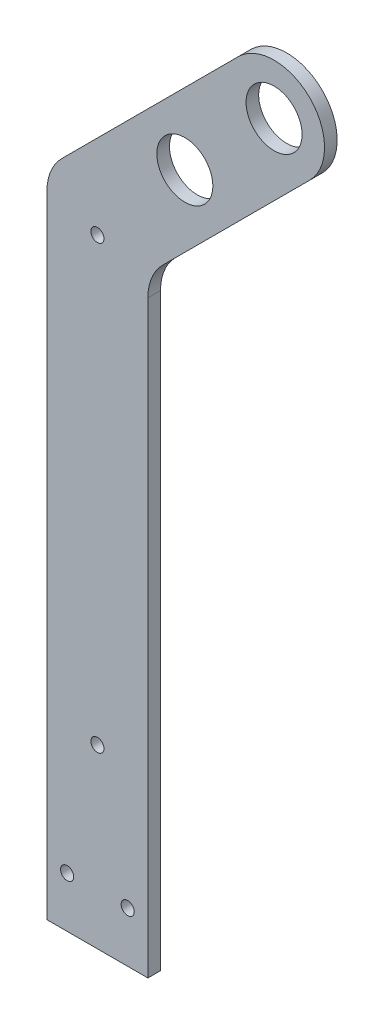
SolidWorks part; units mm, degrees
material "6061 合金"
ref_plane "前视基准面" through (0, 0, 0) normal (0, 0, 1) x (1, 0, 0)
ref_plane "上视基准面" through (0, 0, 0) normal (0, 1, 0) x (1, 0, 0)
ref_plane "右视基准面" through (0, 0, 0) normal (1, 0, 0) x (0, 0, -1)
other "Configuration Table"
sketch "草图1" plane through (0, 0, 0) normal (0, 0, 1) x (1, 0, 0)
  circle A0 centre (0, 0) radius 20
  circle A1 centre (0, 0) radius 11.1
  dimension "D1" = 40
  dimension "D2" = 22.2
extrude "凸台-拉伸1" add sketch "草图1" along normal blind 60 contours A1 | A0 region at (0, 0, 0)
ref_plane "基准面1" through (0, 0, 30) normal (0, 0, 1) x (1, 0, 0)
sketch "草图2" plane through (0, 0, 30) normal (0, 0, 1) x (1, 0, 0)
  line L0 (0, 0) -> (-70, -70) construction
  line L1 (-70, -70) -> (-70, -320) construction
  line L2 (0, -57.3148) -> (0, 49.9409) construction
  line L3 (-56.8582, 0) -> (46.4003, 0) construction
  line L4 (-14.1421, 14.1421) -> (-90, -61.7157)
  line L5 (14.1421, -14.1421) -> (-50, -78.2843)
  line L6 (-90, -61.7157) -> (-90, -320)
  line L7 (-50, -78.2843) -> (-50, -320)
  line L8 (-90, -320) -> (-50, -320)
  circle A2 centre (0, 0) radius 20 construction
  arc A3 (-14.1421, 14.1421) -> (14.1421, -14.1421) centre (0, 0) ccw
  dimension "D1" = 45
  dimension "D2" = 250
  dimension "D3" = 70
  dimension "D4" = 40
  dimension "D5" = 40
extrude "凸台-拉伸2" add sketch "草图2" along normal mid plane 60 contours L7 L8 L6 L4 A3 L5
sketch "草图4" plane through (0, 0, 60) normal (0, 0, 1) x (1, 0, 0)
  line L0 (-90, -61.7157) -> (-90, -320) construction
  line L1 (-90, -290) -> (-50, -290)
  line L2 (-90, -290) -> (-90, -350)
  line L4 (-50, -290) -> (-50, -350)
  line L5 (-50, -78.2843) -> (-50, -320) construction
  line L6 (-90, -320) -> (-50, -320) construction
  arc A0 (-90, -350) -> (-50, -350) centre (-70, -350) ccw
  circle A1 centre (-70, -350) radius 11
  dimension "D3" = 22
  dimension "D1" = 30
  dimension "D2" = 30
extrude "凸台-拉伸3" add sketch "草图4" along normal blind 5
mirror "镜向1" about plane through (0, 0, 30) normal (0, 0, 1) of "凸台-拉伸3"
sketch "草图5" plane through (0, 0, 0) normal (0, 1, 0) x (1, 0, 0)
  line L0 (0, 0) -> (0, -78.0582) construction
ref_plane "基准面2" through (-70, 0, 0) normal (-1, 0, 0) x (0, 0, 1)
sketch "草图7" plane through (-70, 0, 0) normal (-1, 0, 0) x (0, 0, 1)
  line L0 (-34.1239, -350) -> (109.535, -350) construction
sketch "草图8" plane through (0, 0, 60) normal (0, 0, 1) x (1, 0, 0)
  line L0 (0, 0) -> (-70, -70) construction
  circle A0 centre (-35.3553, -35.3553) radius 11.1
  dimension "D1" = 22.2
  dimension "D2" = 50
extrude "切除-拉伸1" cut sketch "草图8" against normal blind 100
fillet "圆角4" radius 20 2 edges at (-90, -61.7157, 30) (-50, -78.2843, 30)
fillet "圆角1" [suppressed] radius 50
fillet "圆角2" [suppressed] radius 3
sketch "草图9" plane through (0, 0, 65) normal (0, 0, 1) x (1, 0, 0)
  circle A0 centre (-70, -350) radius 13
  dimension "D1" = 26
extrude "切除-拉伸2" [suppressed] cut sketch "草图9" against normal blind 0.75
sketch "草图10" plane through (0, 0, -5) normal (0, 0, -1) x (-1, 0, 0)
  circle A0 centre (70, -350) radius 13
  dimension "D1" = 26
extrude "切除-拉伸3" [suppressed] cut sketch "草图10" against normal blind 0.75 contours A0
sketch "草图11" plane through (-90, 0, 0) normal (-1, 0, 0) x (0, 0, 1)
  circle A0 centre (48.5, -118.9949) radius 2.75
  circle A1 centre (48.5, -183.9949) radius 2.75
  circle A2 centre (48.5, -248.9949) radius 2.75
  circle A3 centre (11.5, -248.9949) radius 2.75
  circle A4 centre (11.5, -183.9949) radius 2.75
  circle A5 centre (11.5, -118.9949) radius 2.75
  dimension "D1" = 5.5
extrude "切除-拉伸4" [suppressed] cut sketch "草图11" against normal through all contours A1 | A2 | A0 | A3 | A4 | A5
sketch "草图12" [suppressed] plane through (-90, 0, 0) normal (-1, 0, 0) x (0, 0, 1)
  line L0 (30, -62.0134) -> (30, -339.6946) construction
  line L1 (10, -128.9949) -> (50, -128.9949)
  line L2 (10, -128.9949) -> (10, -173.9949)
  line L3 (10, -173.9949) -> (50, -173.9949)
  line L4 (50, -128.9949) -> (50, -173.9949)
  line L5 (10, -193.9949) -> (50, -193.9949)
  line L6 (10, -193.9949) -> (10, -238.9949)
  line L7 (10, -238.9949) -> (50, -238.9949)
  line L8 (50, -193.9949) -> (50, -238.9949)
  line L9 (10, -258.9949) -> (50, -258.9949)
  line L10 (10, -258.9949) -> (10, -290)
  line L11 (10, -290) -> (50, -290)
  line L12 (50, -258.9949) -> (50, -290)
  line L13 (19.5, -173.9949) -> (40.5, -173.9949)
  line L14 (19.5, -173.9949) -> (19.5, -193.9949)
  line L15 (19.5, -193.9949) -> (40.5, -193.9949)
  line L16 (40.5, -173.9949) -> (40.5, -193.9949)
  line L17 (19.5, -238.9949) -> (40.5, -238.9949)
  line L18 (19.5, -238.9949) -> (19.5, -258.9949)
  line L19 (19.5, -258.9949) -> (40.5, -258.9949)
  line L20 (40.5, -238.9949) -> (40.5, -258.9949)
  line L21 (60, -82.4264) -> (60, -290) construction
  line L22 (0, -290) -> (0, -82.4264) construction
  line L23 (57, -320) -> (3, -320) construction
  circle A0 centre (48.5, -118.9949) radius 2.75 construction
  circle A1 centre (48.5, -183.9949) radius 2.75 construction
  circle A2 centre (48.5, -248.9949) radius 2.75 construction
  dimension "D1" = 10
  dimension "D2" = 10
  dimension "D3" = 10
  dimension "D4" = 8
  dimension "D5" = 10
  dimension "D6" = 10
  dimension "D7" = 10
  dimension "D8" = 30
extrude "减重" [suppressed] cut sketch "草图12" against normal through all contours L0 L1 L2 L3 | L15 L0 L17 L7 L8 L5 | L0 L5 L6 L7 | L19 L0 L11 L12 L9 | L0 L9 L10 L11 | L1 L0 L13 L3 L4
fillet "圆角3" [suppressed] radius 3
sketch "草图13" plane through (0, 0, 60) normal (0, 0, 1) x (1, 0, 0)
  circle A0 centre (0, 0) radius 13
  circle A1 centre (-35.3553, -35.3553) radius 13
  dimension "D1" = 26
  dimension "D2" = 26
extrude "切除-拉伸6" [suppressed] cut sketch "草图13" against normal blind 1.75
sketch "草图14" plane through (0, 0, 0) normal (0, 0, -1) x (-1, 0, 0)
  circle A0 centre (0, 0) radius 13
  circle A1 centre (35.3553, -35.3553) radius 13
  dimension "D1" = 26
  dimension "D2" = 26
extrude "切除-拉伸7" [suppressed] cut sketch "草图14" against normal blind 1.75
sketch "草图15" [suppressed] plane through (0, 0, 0) normal (0, 0, -1) x (-1, 0, 0)
  line L0 (0, 0) -> (70, -350) construction
  line L1 (56.2719, -67.2005) -> (60.1942, -86.8121) construction
  line L2 (70, -350) -> (204.3541, -323.1292) construction
  circle A0 centre (56.2719, -67.2005) radius 2.75
  circle A1 centre (75.2172, -73.6095) radius 2.75
  circle A2 centre (60.1942, -86.8121) radius 2.75
  dimension "D1" = 5.5
  dimension "D2" = 20
  dimension "D3" = 20
  dimension "D4" = 20
  dimension "D5" = 42
  dimension "D6" = 270
extrude "切除-拉伸8" [suppressed] cut sketch "草图15" against normal through all contours A2 | A0 | A1
ref_plane "小腿主干连杆面" through (0, 0, 0) normal (0.9806, -0.1961, 0) x (0, 0, -1)
ref_plane "小腿主干对称面" through (0, 0, 30) normal (0, 0, -1) x (-1, 0, 0)
sketch "草图16" plane through (0, 0, 60) normal (0, 0, 1) x (1, 0, 0)
  line L0 (0, 0) -> (-70, -350)
  line L1 (-35.3553, -35.3553) -> (0, 0)
sketch "草图17" plane through (0, 0, 60) normal (0, 0, 1) x (1, 0, 0)
  line L0 (0, 0) -> (-70, -350) construction
  line L1 (118.6974, 32.5948) -> (32.9122, -396.3312) construction
  line L2 (92.7764, -97.0102) -> (20.2919, -82.5133)
  line L3 (73.1648, -195.0683) -> (0.6803, -180.5713)
  circle A0 centre (20.2919, -82.5133) radius 46
  circle A1 centre (0.6803, -180.5713) radius 46
  dimension "D3" = 92
  dimension "D4" = 92
  dimension "D1" = 110
  dimension "D2" = 73.92
  dimension "D5" = 180
  dimension "D6" = 280
sketch "草图18" plane through (0, 0, 60) normal (0, 0, 1) x (1, 0, 0)
  line L1 (14.1421, -14.1421) -> (-44.1421, -72.4264) construction
  line L3 (14.1421, -14.1421) -> (-44.1421, -72.4264)
  line L4 (15.4873, -12.6548) -> (52.8188, -49.9864)
  line L5 (-50, -128.5133) -> (20.2919, -128.5133)
  line L10 (-90, -290) -> (-50, -290)
  line L11 (-50, -290) -> (-50, -86.5685)
  line L12 (-44.1421, -72.4264) -> (14.1421, -14.1421)
  line L13 (-14.1421, 14.1421) -> (-84.1421, -55.8579)
  line L14 (-90, -70) -> (-90, -290)
  line L16 (-50, -128.5133) -> (-50, -86.5685)
  line L17 (-44.1421, -72.4264) -> (14.1421, -14.1421)
  circle A0 centre (20.2919, -82.5133) radius 46 construction
  arc A1 (14.1421, -14.1421) -> (-14.1421, 14.1421) centre (0, 0) ccw construction
  arc A2 (14.1421, -14.1421) -> (-14.1421, 14.1421) centre (0, 0) ccw
  arc A3 (14.1421, -14.1421) -> (15.4873, -12.6548) centre (0, 0) ccw
  arc A4 (20.2919, -128.5133) -> (52.8188, -49.9864) centre (20.2919, -82.5133) ccw
  circle A5 centre (20.2919, -82.5133) radius 35
  arc A9 (-84.1421, -55.8579) -> (-90, -70) centre (-70, -70) ccw
  arc A10 (-84.1421, -55.8579) -> (-90, -70) centre (-70, -70) ccw
  arc A11 (-44.1421, -72.4264) -> (-50, -86.5685) centre (-30, -86.5685) ccw
  arc A12 (-44.1421, -72.4264) -> (-50, -86.5685) centre (-30, -86.5685) ccw
  line M14 (-50, -290) -> (-50, -86.5685)
  line M15 (-44.1421, -72.4264) -> (14.1421, -14.1421)
  arc M16 (14.1421, -14.1421) -> (-14.1421, 14.1421) centre (0, 0) ccw
  arc M22 (-50, -86.5685) -> (-44.1421, -72.4264) centre (-30, -86.5685) cw
  dimension "D2" = 70
  dimension "D1" = 0
extrude "凸台-拉伸4" add sketch "草图18" against normal blind 5 from offset 25 contours L5 A4 L4 A5 M16 M15 M22 M14 region at (16.0508, -14.5165, 60) offset against normal yes
sketch "草图19" plane through (0, 0, 0) normal (0, 0, -1) x (-1, 0, 0)
  line L0 (50, -86.5685) -> (50, -290) construction
  line L1 (50, -134.5713) -> (50, -226.5713)
  line L2 (-0.6803, -134.5713) -> (50, -134.5713)
  line L3 (-0.6803, -226.5713) -> (50, -226.5713)
  circle A0 centre (-0.6803, -180.5713) radius 46 construction
  arc A1 (-0.6803, -134.5713) -> (-0.6803, -226.5713) centre (-0.6803, -180.5713) ccw
  circle A2 centre (-0.6803, -180.5713) radius 35
  dimension "D1" = 70
extrude "凸台-拉伸5" add sketch "草图19" against normal blind 5 from offset 25 offset against normal yes
fillet "圆角5" radius 10 2 edges at (-50, -226.5713, 27.5) (-50, -128.5133, 32.5)
sketch "草图21" plane through (0, 0, 65) normal (0, 0, 1) x (1, 0, 0)
  line L0 (-70, -350) -> (-70, -6.9331) construction
  circle A0 centre (-70, -75) radius 2.6
  circle A1 centre (-70, -250) radius 2.6
  circle A2 centre (-58, -300) radius 2.6
  circle A3 centre (-82, -300) radius 2.6
  dimension "D1" = 5.2
  dimension "D2" = 12
  dimension "D3" = 50
  dimension "D4" = 100
  dimension "D5" = 175
extrude "切除-拉伸9" cut sketch "草图21" against normal through all both and the other way through all
sketch "草图22" plane through (-90, 0, 0) normal (-1, 0, 0) x (0, 0, 1)
  line L0 (-5, -350) -> (-5, -370) construction
  line L5 (-5, -387.1281) -> (35, -387.1281)
  line L6 (-5, -387.1281) -> (-5, 64.9179)
  line L7 (-5, 64.9179) -> (35, 64.9179)
  line L8 (35, -387.1281) -> (35, 64.9179)
  line L10 (65, -370) -> (40, -370)
  line L11 (65, -370) -> (65, 61.088)
  line L12 (65, 61.088) -> (40, 61.088)
  line L13 (40, -370) -> (40, 61.088)
  dimension "D1" = 25
  dimension "D2" = 5
extrude "切除-拉伸10" cut sketch "草图22" against normal through all both contours L8 L7 L6 L5 | L13 L12 L11 L10
